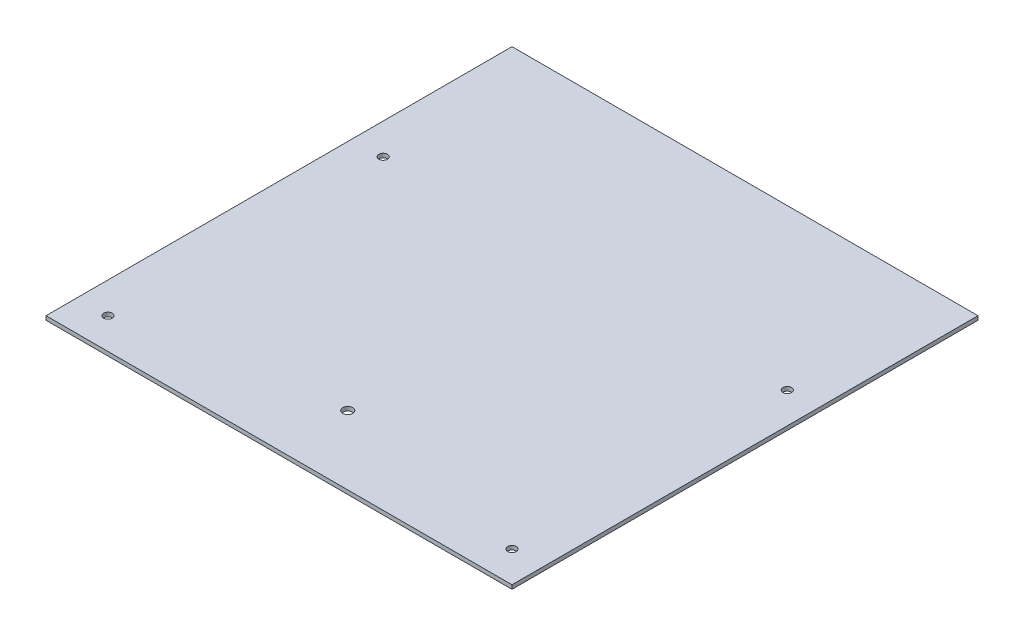
SolidWorks part; units mm, degrees
ref_plane "Front Plane" through (0, 0, 0) normal (0, 0, 1) x (1, 0, 0)
ref_plane "Top Plane" through (0, 0, 0) normal (0, 1, 0) x (1, 0, 0)
ref_plane "Right Plane" through (0, 0, 0) normal (1, 0, 0) x (0, 0, -1)
sketch "Sketch1" plane through (0, 0, 0) normal (0, 1, 0) x (1, 0, 0)
  line L1 (-175, 175) -> (175, 175)
  line L2 (-175, 175) -> (-175, -175)
  line L3 (-175, -175) -> (175, -175)
  line L4 (175, 175) -> (175, -175)
  line L5 (-175, 175) -> (175, -175) construction
  line L6 (-175, -175) -> (175, 175) construction
  point P0 (0, 0)
  dimension "D1" = 350
extrude "Boss-Extrude1" add sketch "Sketch1" along normal blind 3
sketch "Sketch2" plane through (0, 3, 0) normal (0, 1, 0) x (1, 0, 0)
  line L0 (-175, 175) -> (-175, 55) construction
  line L1 (-175, 175) -> (-175, -175) construction
  line L2 (-175, 55) -> (175, 55) construction
  line L3 (175, -175) -> (175, 175) construction
  line L4 (-155, -175) -> (-155, -155) construction
  line L5 (-175, -175) -> (175, -175) construction
  line L6 (-155, -155) -> (155, -155) construction
  line L7 (155, -155) -> (155, -175) construction
  line L8 (-155, -155) -> (-155, -151.75) construction
  line L9 (155, -155) -> (155, -151.75) construction
  line L10 (155, -151.75) -> (-155, -151.75) construction
  line L11 (-151.75, 55) -> (-151.75, -151.75) construction
  line L12 (-151.75, -151.75) -> (151.75, 55) construction
  line L13 (151.75, 55) -> (151.75, -151.75) construction
  line L14 (151.75, -151.75) -> (-151.75, 55) construction
  line L15 (0, -48.375) -> (0, -123.375) construction
  circle A1 centre (-151.75, -151.75) radius 3.25
  circle A2 centre (151.75, -151.75) radius 3.25
  circle A3 centre (151.75, 55) radius 3.25
  circle A4 centre (-151.75, 55) radius 3.25
  circle A6 centre (0, -123.375) radius 3.75
  point P8 (-155, 55)
  point P9 (155, 55)
  dimension "D6" = 6.5
  dimension "D7" = 7.5
  dimension "D1" = 120
  dimension "D2" = 20
  dimension "D3" = 20
  dimension "D4" = 20
  dimension "D5" = 75
extrude "Cut-Extrude1" cut sketch "Sketch2" against normal up to surface (3 mm away) up to face at (0, 0, 0)
